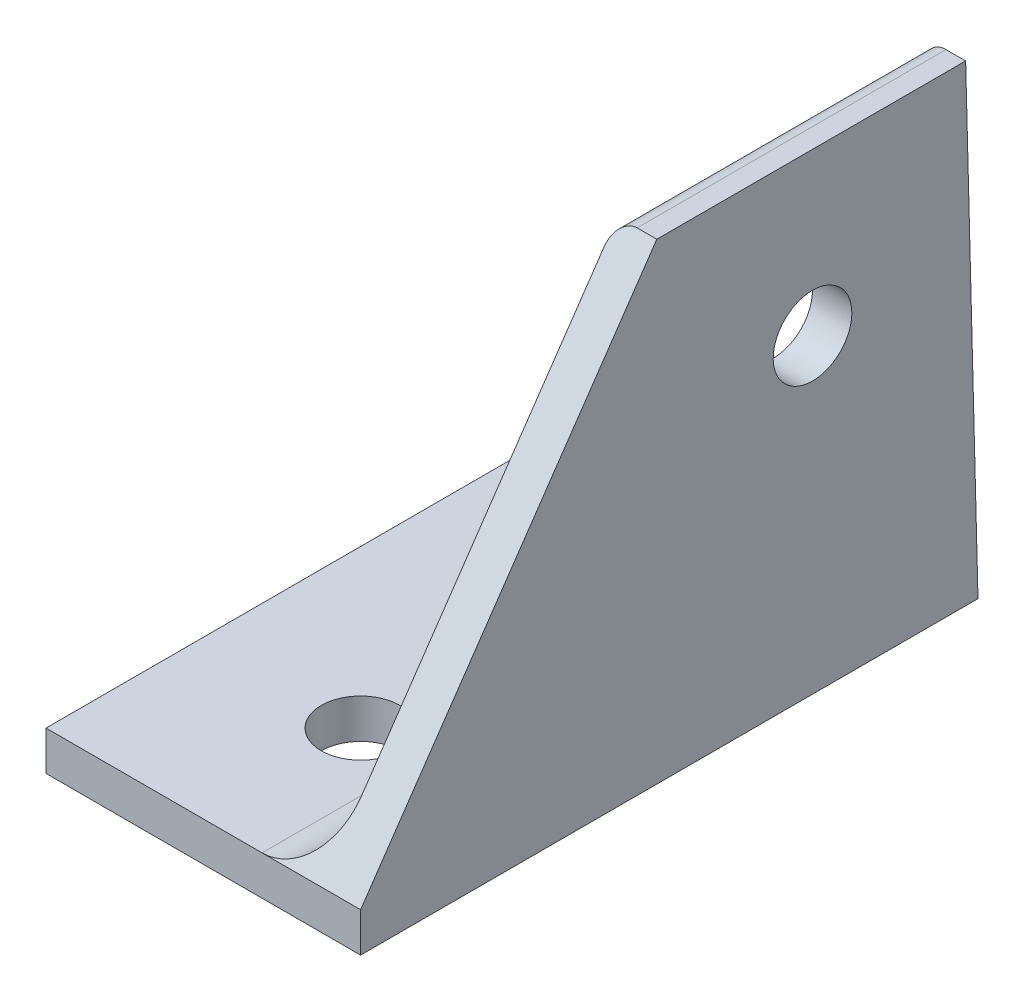
SolidWorks part; units mm, degrees
ref_plane "Front Plane" through (0, 0, 0) normal (0, 0, 1) x (1, 0, 0)
ref_plane "Top Plane" through (0, 0, 0) normal (0, 1, 0) x (1, 0, 0)
ref_plane "Right Plane" through (0, 0, 0) normal (1, 0, 0) x (0, 0, -1)
sketch "Sketch0" plane through (0, 0, 0) normal (0, 0, 1) x (1, 0, 0)
  line L0 (-19.05, -19.05) -> (19.05, -19.05)
  line L1 (19.05, -19.05) -> (19.05, 19.05)
  line L2 (19.05, 0) -> (0, 0) construction
  line L3 (0, 0) -> (0, -19.05) construction
  line L4 (15.875, -11.0998) -> (15.875, 19.05) construction
  line L5 (11.0998, -15.875) -> (-19.05, -15.875) construction
  arc A0 (15.875, -11.0998) -> (11.0998, -15.875) centre (11.0998, -11.0998) cw
  point P3 (14.4764, -14.4764)
  dimension "Inside Corner Radius" = 4.7752
  dimension "Outside Height" = 38.1
  dimension "Inside Height" = 34.925
  dimension "Inside Width" = 34.925
  dimension "Wall Thickness" = 3.175
  dimension "D1" = 3.175
  dimension "Outside Width" = 38.1
sketch "Sketch1" plane through (0, 0, 0) normal (1, 0, 0) x (0, 0, -1)
  line L0 (25.4, 0) -> (-25.4, 0)
  point P4 (0, 0)
  dimension "Length" = 50.8
sketch "Sketch2" plane through (0, 0, 0) normal (0, 0, 1) x (1, 0, 0)
  line L0 (-19.05, -19.05) -> (19.05, -19.05)
  line L1 (19.05, -19.05) -> (19.05, 19.05)
  line L2 (19.05, 19.05) -> (15.875, 19.05) construction
  line L3 (15.875, 17.4625) -> (15.875, -11.0998)
  line L4 (11.0998, -15.875) -> (-17.4625, -15.875)
  line L5 (-19.05, -19.05) -> (-19.05, -15.875) construction
  line L6 (17.4625, 19.05) -> (19.05, 19.05)
  line L7 (-19.05, -17.4625) -> (-19.05, -19.05)
  line L8 (19.05, 0) -> (0, 0) construction
  line L9 (0, 0) -> (0, -19.05) construction
  arc A0 (15.875, 17.4625) -> (17.4625, 19.05) centre (17.4625, 17.4625) cw
  arc A1 (-19.05, -17.4625) -> (-17.4625, -15.875) centre (-17.4625, -17.4625) cw
  arc A2 (15.875, -11.0998) -> (11.0998, -15.875) centre (11.0998, -11.0998) cw
  dimension "Inside Radius" = 4.7752
  dimension "Height" = 38.1
  dimension "Width" = 38.1
  dimension "Thickness" = 3.175
extrude "Boss-Extrude1" add sketch "Sketch2" along normal mid plane 50.8
sketch "Break Locations" plane through (0, 0, 0) normal (1, 0, 0) x (0, 0, -1)
  line L0 (13.462, 0) -> (-13.462, 0)
  line L1 (-25.4, -19.05) -> (-25.4, 19.05) construction
  line L2 (25.4, -19.05) -> (25.4, 19.05) construction
  point P0 (6.985, 0)
  point P1 (-6.985, 0)
  point P10 (0, 0)
  point P11 (-13.462, 0)
  point P13 (13.462, 0)
  dimension "D1" = 32.385
  dimension "D2" = 32.385
  dimension "D3" = 38.862
sketch "Sketch3" plane through (0, -19.05, 0) normal (0, -1, 0) x (1, 0, 0)
  line L0 (19.05, 25.4) -> (6.35, 25.4) construction
  line L1 (-19.05, 25.4) -> (19.05, 25.4) construction
  line L2 (6.35, 25.4) -> (6.35, 12.7) construction
  line L3 (6.35, 12.7) -> (6.35, -12.7) construction
  line L4 (-19.05, 25.4) -> (-6.35, 25.4)
  line L5 (-6.35, 25.4) -> (-6.35, -25.4)
  line L6 (-19.05, -25.4) -> (19.05, -25.4) construction
  line L7 (-6.35, -25.4) -> (-19.05, -25.4)
  line L8 (-19.05, -25.4) -> (-19.05, 25.4)
  circle A0 centre (6.35, 12.7) radius 3.175
  circle A1 centre (6.35, -12.7) radius 3.175
  dimension "D4" = 12.7
  dimension "D1" = 12.7
  dimension "D2" = 12.7
  dimension "D3" = 25.4
extrude "Cut-Extrude1" cut sketch "Sketch3" against normal through all
sketch "Sketch12" plane through (19.05, 0, 0) normal (1, 0, 0) x (0, 0, -1)
  line L0 (23.4518, 19.05) -> (24.4495, -19.05)
  line L1 (24.3992, -17.1295) -> (10.8021, 502.1225) construction
  line L2 (-25.4, 19.05) -> (25.4, 19.05) construction
  line L3 (-25.4, -19.05) -> (25.4, -19.05) construction
  line L5 (-1.4842, 19.05) -> (-25.4, -15.875)
  line L6 (-25.4, -19.05) -> (-25.4, 19.05) construction
  line L7 (-25.4, -15.875) -> (-25.4, -19.05)
  line L8 (-25.4, -19.05) -> (24.4495, -19.05)
  line L9 (23.4518, 19.05) -> (-1.4842, 19.05)
  dimension "D1" = 3.175
extrude "Cut-Extrude2" cut sketch "Sketch12" against normal through all flip side to cut
sketch "Sketch13" plane through (19.05, 0, 0) normal (1, 0, 0) x (0, 0, -1)
  line L0 (10.7562, 18.7176) -> (11.0886, 6.0219) construction
  circle A0 centre (11.0886, 6.0219) radius 3.175
extrude "Cut-Extrude3" cut sketch "Sketch13" against normal through all
sketch "Sketch14" plane through (0, -15.875, 0) normal (0, 1, 0) x (1, 0, 0)
  circle A0 centre (6.35, -12.7) radius 6.35
  circle A1 centre (6.35, 12.7) radius 6.35
extrude "Cut-Extrude4" cut sketch "Sketch14" along normal blind 2.54
equation "\"D1@Break Locations\" = .85 * \"Height@Sketch2\""
equation "\"D2@Break Locations\"=\"D1@Break Locations\""
equation "\"Thickness@Sketch2\"=\"wall thickness@sketch0\""
equation "\"Height@Sketch2\"=\"outside height@sketch0\""
equation "\"Width@Sketch2\"=\"outside width@sketch0\""
equation "\"Inside Radius@Sketch2\"=\"inside corner radius@sketch0\""
equation "\"Length@Boss-Extrude1\"=\"length@sketch1\""
equation "\"D3@Break Locations\"=\"D2@Break Locations\"*1.2"
equation "\"D1@Sketch0\"=\"Wall Thickness@Sketch0\""
